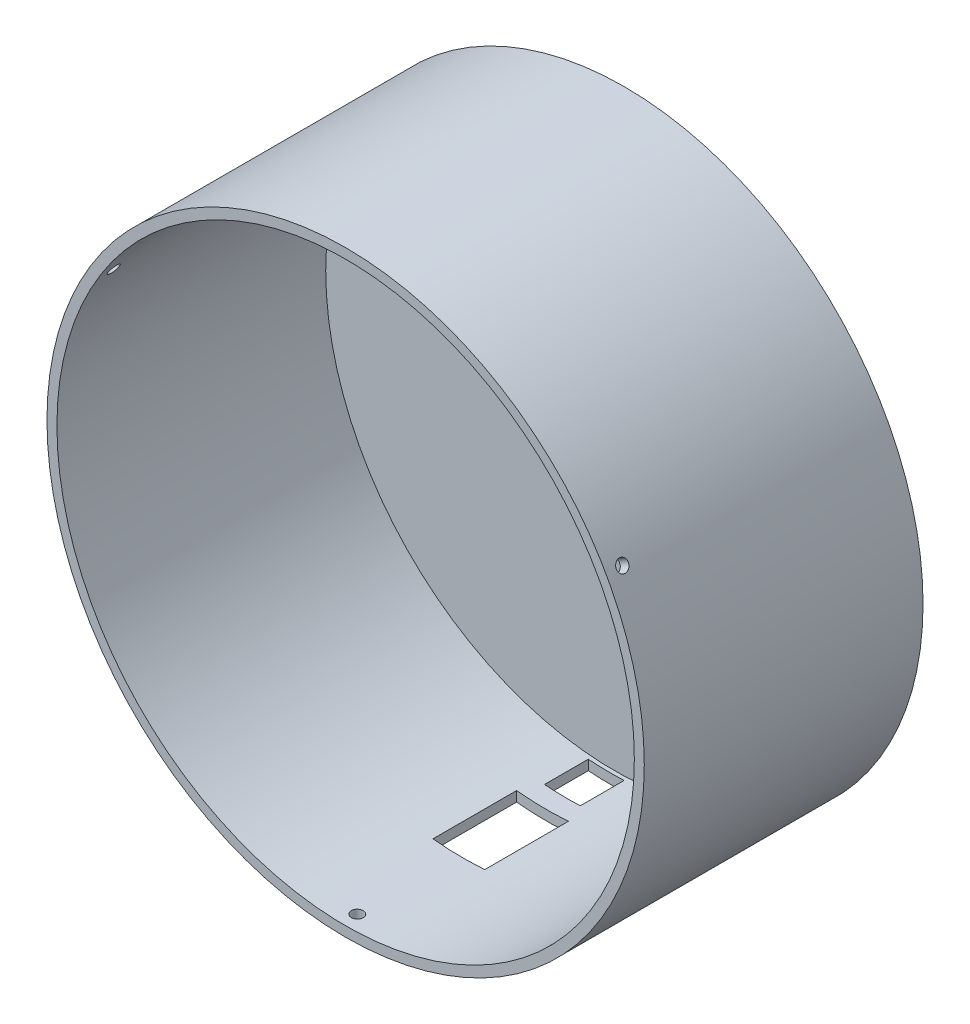
SolidWorks part; units mm, degrees
ref_plane "Płaszczyzna przednia" through (0, 0, 0) normal (0, 0, 1) x (1, 0, 0)
ref_plane "Płaszczyzna górna" through (0, 0, 0) normal (0, 1, 0) x (1, 0, 0)
ref_plane "Płaszczyzna prawa" through (0, 0, 0) normal (1, 0, 0) x (0, 0, -1)
sketch "Szkic1" plane through (0, 0, 0) normal (0, 0, 1) x (1, 0, 0)
  circle A0 centre (0, 0) radius 75
  dimension "D1" = 150
extrude "Dodanie-wyciągnięcie1" add sketch "Szkic1" along normal blind 70
shell "Skorupa1" thickness 2.5 removed face at (75, 0, 70)
ref_plane "Płaszczyzna1" through (0, -75, 0) normal (0, -1, 0) x (-1, 0, 0)
sketch "Szkic3" plane through (0, -75, 0) normal (0, -1, 0) x (-1, 0, 0)
  line L0 (75, 0) -> (-75, 0) construction
  line L1 (7.5614, -19.5) -> (-5.4386, -19.5)
  line L2 (7.5614, -19.5) -> (7.5614, -40.5)
  line L3 (7.5614, -40.5) -> (-5.4386, -40.5)
  line L4 (-5.4386, -19.5) -> (-5.4386, -40.5)
  line L5 (7.5614, -19.5) -> (-5.4386, -40.5) construction
  line L6 (7.5614, -40.5) -> (-5.4386, -19.5) construction
  point P0 (1.0614, -30)
  dimension "D1" = 13
  dimension "D2" = 21
  dimension "D3" = 30
extrude "Wytnij-wyciągnięcie1" cut sketch "Szkic3" against normal blind 60
sketch "Szkic4" plane through (0, -75, 0) normal (0, -1, 0) x (-1, 0, 0)
  line L1 (5.5614, -14.5) -> (-3.4386, -14.5)
  line L2 (5.5614, -14.5) -> (5.5614, -3.5)
  line L3 (5.5614, -3.5) -> (-3.4386, -3.5)
  line L4 (-3.4386, -14.5) -> (-3.4386, -3.5)
  line L5 (5.5614, -14.5) -> (-3.4386, -3.5) construction
  line L6 (5.5614, -3.5) -> (-3.4386, -14.5) construction
  line L7 (-5.4386, -19.5) -> (7.5614, -19.5) construction
  line L9 (7.5614, -19.5) -> (7.5614, -40.5) construction
  point P0 (1.0614, -9)
  dimension "D1" = 9
  dimension "D2" = 11
  dimension "D3" = 5
  dimension "D4" = 6.5
extrude "Wytnij-wyciągnięcie2" cut sketch "Szkic4" against normal blind 60
sketch "Szkic5" plane through (0, -75, 0) normal (0, -1, 0) x (-1, 0, 0)
  line L2 (-75, -70) -> (75, -70) construction
  line L3 (-5.4386, -40.5) -> (-5.4386, -19.5) construction
  circle A0 centre (1.0614, -66) radius 1.5
  dimension "D1" = 3
  dimension "D2" = 4
  dimension "D3" = 6.5
extrude "Wytnij-wyciągnięcie3" cut sketch "Szkic5" against normal blind 60
pattern_circular "Szyk kołowy1" count 3 over 360 about axis through (0, 0, 70) along (0, 0, 1) of "Wytnij-wyciągnięcie3"
